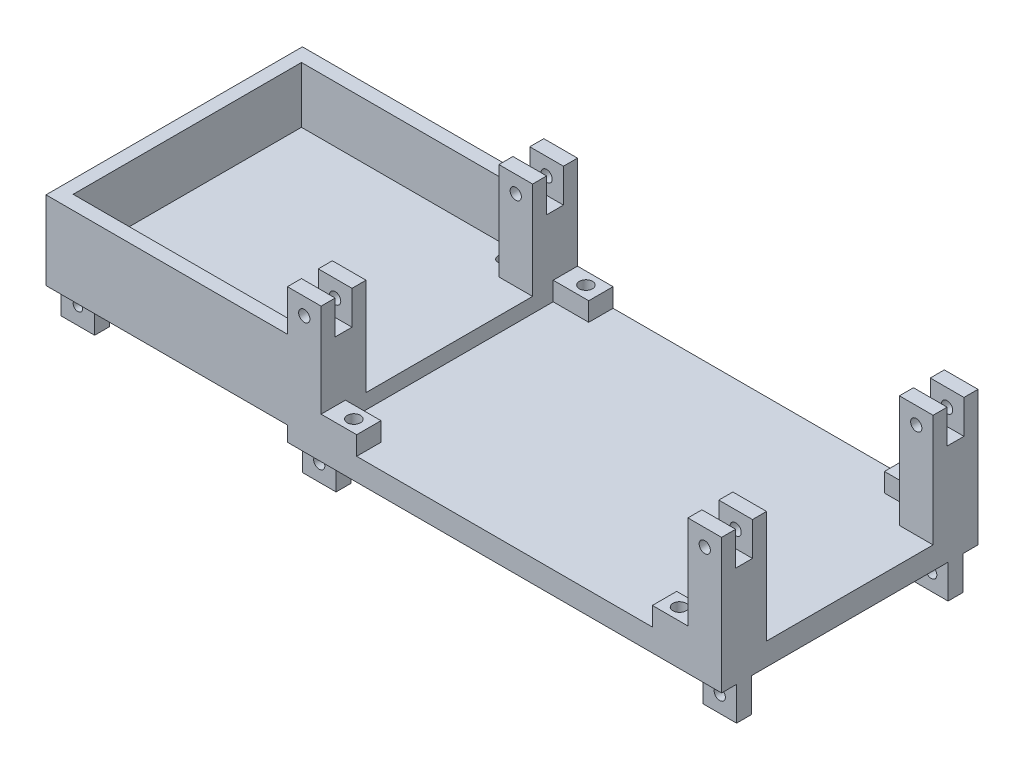
SolidWorks part; units mm, degrees
ref_plane "Front Plane" through (0, 0, 0) normal (0, 0, 1) x (1, 0, 0)
ref_plane "Top Plane" through (0, 0, 0) normal (0, 1, 0) x (1, 0, 0)
ref_plane "Right Plane" through (0, 0, 0) normal (1, 0, 0) x (0, 0, -1)
sketch "Sketch1" plane through (0, 0, 0) normal (0, 1, 0) x (1, 0, 0)
  line L1 (0, 0) -> (-116, 0)
  line L2 (0, 0) -> (0, 34.25)
  line L3 (0, 34.25) -> (-116, 34.25)
  line L4 (-116, 0) -> (-116, 34.25)
  dimension "D1" = 116
  dimension "D2" = 34.25
extrude "Boss-Extrude2" add sketch "Sketch1" along normal blind 6
sketch "Sketch3" plane through (0, 0, 0) normal (0, -1, 0) x (1, 0, 0)
  line L0 (-116, -34.25) -> (-116, 0) construction
  line L1 (-116, -4) -> (-107, -4)
  line L2 (-116, -4) -> (-116, -8)
  line L3 (-116, -8) -> (-107, -8)
  line L4 (-107, -4) -> (-107, -8)
  line L5 (0, 0) -> (0, -34.25) construction
  line L6 (0, -4) -> (-9, -4)
  line L7 (0, -4) -> (0, -8)
  line L8 (0, -8) -> (-9, -8)
  line L9 (-9, -4) -> (-9, -8)
  line L10 (-116, 0) -> (0, 0) construction
  dimension "D1" = 4
  dimension "D2" = 4
  dimension "D3" = 9
  dimension "D4" = 9
  dimension "D5" = 4
  dimension "D6" = 4
extrude "Boss-Extrude3" add sketch "Sketch3" along normal blind 9
sketch "Sketch4" plane through (0, 0, -4) normal (0, 0, 1) x (1, 0, 0)
  line L0 (-116, -9) -> (-116, 0) construction
  line L1 (-107, -9) -> (-116, -9) construction
  line L2 (0, -9) -> (-9, -9) construction
  line L3 (0, -9) -> (0, 0) construction
  circle A0 centre (-111.5, -4.5) radius 1.5
  circle A1 centre (-4.5, -4.5) radius 1.5
  dimension "D1" = 3
  dimension "D2" = 4.5
  dimension "D3" = 4.5
  dimension "D4" = 4.5
  dimension "D5" = 3
  dimension "D6" = 4.5
extrude "Cut-Extrude1" cut sketch "Sketch4" against normal through all
sketch "Sketch5" plane through (0, 6, 0) normal (0, 1, 0) x (1, 0, 0)
  line L1 (-116, 0) -> (-107, 0)
  line L2 (-116, 0) -> (-116, 12)
  line L3 (-116, 12) -> (-107, 12)
  line L4 (-107, 0) -> (-107, 12)
  line L5 (0, 0) -> (-9, 0)
  line L6 (0, 0) -> (0, 12)
  line L7 (0, 12) -> (-9, 12)
  line L8 (-9, 0) -> (-9, 12)
  dimension "D1" = 12
  dimension "D2" = 9
  dimension "D3" = 9
  dimension "D4" = 12
extrude "Boss-Extrude4" add sketch "Sketch5" along normal blind 30
sketch "Sketch6" plane through (0, 36, 0) normal (0, 1, 0) x (1, 0, 0)
  line L0 (-116, 12) -> (-116, 0) construction
  line L1 (-116, 8.25) -> (-107, 8.25)
  line L2 (-116, 8.25) -> (-116, 3.75)
  line L3 (-116, 3.75) -> (-107, 3.75)
  line L4 (-107, 8.25) -> (-107, 3.75)
  line L5 (-107, 0) -> (-107, 12) construction
  line L6 (-9, 12) -> (-9, 0) construction
  line L7 (-9, 8.25) -> (0, 8.25)
  line L8 (-9, 8.25) -> (-9, 3.75)
  line L9 (-9, 3.75) -> (0, 3.75)
  line L10 (0, 8.25) -> (0, 3.75)
  line L11 (0, 0) -> (0, 12) construction
  line L12 (0, 12) -> (-9, 12) construction
  dimension "D1" = 3.75
  dimension "D2" = 4.5
extrude "Cut-Extrude2" cut sketch "Sketch6" against normal blind 9
sketch "Sketch7" plane through (0, 0, 0) normal (0, 0, 1) x (1, 0, 0)
  line L0 (-116, 36) -> (-116, 0) construction
  line L2 (-116, 36) -> (-107, 36) construction
  line L4 (-9, 36) -> (-9, 6) construction
  circle A0 centre (-111.5, 31.5) radius 1.5
  circle A1 centre (-4.5, 31.5) radius 1.5
  dimension "D1" = 3
  dimension "D2" = 4.5
  dimension "D3" = 4.5
  dimension "D4" = 4.5
extrude "Cut-Extrude3" cut sketch "Sketch7" against normal blind 12
sketch "Sketch8" plane through (0, 6, 0) normal (0, 1, 0) x (1, 0, 0)
  line L0 (-107, 0) -> (-107, 12) construction
  line L1 (-107, 0) -> (-9, 0) construction
  circle A0 centre (-14.5, 3.25) radius 1.75
  circle A1 centre (-101.5, 3.25) radius 1.75
  dimension "D1" = 3.5
  dimension "D2" = 5.5
  dimension "D3" = 3.25
  dimension "D4" = 87
extrude "Cut-Extrude4" cut sketch "Sketch8" against normal through all
sketch "Sketch9" plane through (0, 6, 0) normal (0, 1, 0) x (1, 0, 0)
  line L1 (-107, 0) -> (-97.5, 0)
  line L2 (-107, 0) -> (-107, 6.5)
  line L3 (-107, 6.5) -> (-97.5, 6.5)
  line L4 (-97.5, 0) -> (-97.5, 6.5)
  line L5 (-9, 0) -> (-18.5, 0)
  line L6 (-9, 0) -> (-9, 6.5)
  line L7 (-9, 6.5) -> (-18.5, 6.5)
  line L8 (-18.5, 0) -> (-18.5, 6.5)
  circle A0 centre (-14.5, 3.25) radius 1.75 construction
  circle A1 centre (-101.5, 3.25) radius 1.75 construction
  circle A2 centre (-14.5, 3.25) radius 1.75
  circle A3 centre (-101.5, 3.25) radius 1.75
  dimension "D2" = 4
  dimension "D4" = 3.25
  dimension "D5" = 3.25
  dimension "D6" = 3.25
  dimension "D1" = 9.5
  dimension "D3" = 9.5
extrude "Boss-Extrude5" add sketch "Sketch9" along normal blind 5
mirror "Mirror1" about plane through (0, 6, -34.25) normal (0, 0, 1) of "Boss-Extrude5", "Cut-Extrude4", "Boss-Extrude2", "Cut-Extrude1", "Boss-Extrude4", "Cut-Extrude2", "Cut-Extrude3", "Boss-Extrude3"
sketch "Sketch10" plane through (0, 6, 0) normal (0, 1, 0) x (1, 0, 0)
  line L1 (-107, 12) -> (-116, 12)
  line L2 (-107, 12) -> (-107, 56.5)
  line L3 (-107, 56.5) -> (-116, 56.5)
  line L4 (-116, 12) -> (-116, 56.5)
extrude "Boss-Extrude6" add sketch "Sketch10" along normal blind 4
sketch "Sketch11" plane through (-116, 0, 0) normal (-1, 0, 0) x (0, 0, 1)
  line L0 (-68.5, 36) -> (-68.5, 0) construction
  line L1 (-68.5, 10) -> (0, 10)
  line L2 (-68.5, 10) -> (-68.5, 4)
  line L3 (-68.5, 4) -> (0, 4)
  line L4 (0, 10) -> (0, 4)
  line L5 (0, 36) -> (0, 0) construction
  line L6 (-56.5, 10) -> (-12, 10) construction
  line L7 (-60.5, 0) -> (-8, 0) construction
  dimension "D1" = 6
extrude "Boss-Extrude7" add sketch "Sketch11" along normal blind 64.5
sketch "Sketch12" plane through (0, 10, 0) normal (0, 1, 0) x (1, 0, 0)
  line L0 (-116, 68.5) -> (-116, 64.75)
  line L1 (-116, 56.5) -> (-116, 68.5) construction
  line L2 (-116, 64.75) -> (-177, 64.75)
  line L3 (-177, 64.75) -> (-177, 3.75)
  line L4 (-177, 3.75) -> (-116, 3.75)
  line L6 (-116, 3.75) -> (-116, 0)
  line L7 (-116, 0) -> (-180.5, 0)
  line L8 (-180.5, 0) -> (-180.5, 68.5)
  line L9 (-180.5, 68.5) -> (-116, 68.5)
  line L10 (-116, 0) -> (-116, 12) construction
  dimension "D1" = 61
  dimension "D2" = 3.75
  dimension "D3" = 61
extrude "Boss-Extrude8" add sketch "Sketch12" along normal blind 15
sketch "Sketch13" plane through (0, 0, 0) normal (0, 0, 1) x (1, 0, 0)
  line L0 (-116, 0) -> (-116, 4)
  line L1 (-116, 4) -> (-128, 4)
  line L2 (-180.5, 4) -> (-116, 4) construction
  line L3 (-128, 4) -> (-116, 0)
  dimension "D1" = 12
extrude "Boss-Extrude9" add sketch "Sketch13" against normal blind 56
sketch "Sketch14" plane through (0, 4, 0) normal (0, -1, 0) x (1, 0, 0)
  line L0 (-180.5, -68.5) -> (-180.5, 0) construction
  line L1 (-180.5, -4) -> (-171.5, -4)
  line L2 (-180.5, -4) -> (-180.5, -8)
  line L3 (-180.5, -8) -> (-171.5, -8)
  line L4 (-171.5, -4) -> (-171.5, -8)
  line L5 (-180.5, -68.5) -> (-116, -68.5) construction
  line L6 (-180.5, -60.5) -> (-171.5, -60.5)
  line L7 (-180.5, -60.5) -> (-180.5, -64.5)
  line L8 (-180.5, -64.5) -> (-171.5, -64.5)
  line L9 (-171.5, -60.5) -> (-171.5, -64.5)
  line L10 (-180.5, 0) -> (-128, 0) construction
  dimension "D1" = 4
  dimension "D2" = 4
  dimension "D3" = 9
  dimension "D4" = 9
  dimension "D5" = 4
  dimension "D6" = 4
extrude "Boss-Extrude10" add sketch "Sketch14" along normal blind 9
sketch "Sketch15" plane through (0, 0, -64.5) normal (0, 0, -1) x (-1, 0, 0)
  line L0 (180.5, -5) -> (171.5, -5) construction
  line L1 (180.5, -5) -> (180.5, 4) construction
  circle A0 centre (176, -0.5) radius 1.25
  dimension "D1" = 2.5
  dimension "D2" = 4.5
  dimension "D3" = 4.5
extrude "Cut-Extrude5" cut sketch "Sketch15" against normal through all
sketch "Sketch16" plane through (0, 0, 0) normal (0, 0, 1) x (1, 0, 0)
  line L0 (-116, 0) -> (-128, 4)
  line L1 (-128, 4) -> (-116, 4)
  line L2 (-116, 4) -> (-116, 0)
extrude "Cut-Extrude6" cut sketch "Sketch16" against normal blind 13
sketch "Sketch17" plane through (0, 10, 0) normal (0, 1, 0) x (1, 0, 0)
  line L0 (-116, 56.5) -> (-116, 64.75) construction
  line L1 (-177, 64.75) -> (-116, 64.75) construction
  line L4 (-116, 3.75) -> (-177, 3.75) construction
  circle A0 centre (-119.5, 61.25) radius 1.5
  circle A1 centre (-119.5, 7.25) radius 1.5
  dimension "D1" = 3
  dimension "D2" = 3.5
  dimension "D3" = 3.5
  dimension "D4" = 3.5
  dimension "D5" = 3
extrude "Cut-Extrude7" cut sketch "Sketch17" against normal through all
